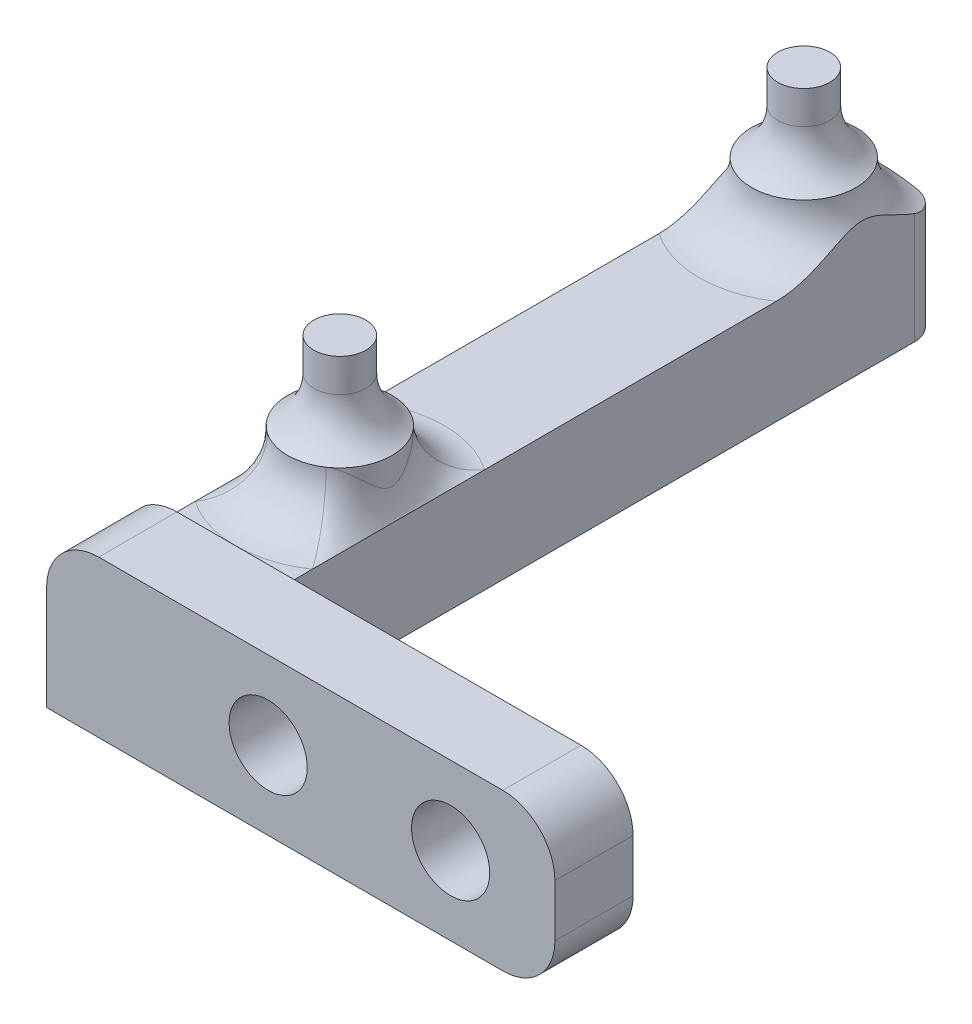
SolidWorks part; units mm, degrees
ref_plane "Front Plane" through (0, 0, 0) normal (0, 0, 1) x (1, 0, 0)
ref_plane "Top Plane" through (0, 0, 0) normal (0, 1, 0) x (1, 0, 0)
ref_plane "Right Plane" through (0, 0, 0) normal (1, 0, 0) x (0, 0, -1)
sketch "Sketch1" plane through (0, 0, 0) normal (0, 1, 0) x (1, 0, 0)
  line L0 (0, 0) -> (0, 15.9628) construction
  line L2 (-2.25, 15.1926) -> (2.25, 15.1926)
  line L3 (-2.25, 15.1926) -> (-2.25, -8.6074)
  line L4 (-2.25, -8.6074) -> (2.25, -8.6074)
  line L5 (2.25, 15.1926) -> (2.25, -8.6074)
  line L6 (-2.25, -8.6074) -> (2.25, -8.6074)
  line L7 (-2.25, -8.6074) -> (-2.25, -14.6074)
  line L8 (-2.25, -14.6074) -> (2.25, -14.6074)
  line L9 (2.25, -8.6074) -> (2.25, -14.6074)
  circle A0 centre (0, 12.1926) radius 2
  circle A1 centre (0, -5.6074) radius 2
  dimension "D1" = 2.25
  dimension "D3" = 4
  dimension "D4" = 4
  dimension "D5" = 3
  dimension "D6" = 3
  dimension "D7" = 17.8
  dimension "D2" = 4.5
  dimension "D8" = 6
extrude "Boss-Extrude1" add sketch "Sketch1" along normal blind 4 contours L9 L4 L7 L8 | A0 L2 L3 L4 L5 A1 region at (0, 0, -3.2926) region at (0, 0, 11.6074)
extrude "Boss-Extrude2" add sketch "Sketch1<3>" along normal blind 6 contours A1 | A0 L0 | L0 A0 region at (-0.8488, 0, -12.1926) region at (0.8488, 0, -12.1926) region at (0, 0, 5.6074)
sketch "Sketch1<3>" plane through (0, 0, 0) normal (0, 1, 0) x (1, 0, 0) same geometry as "Sketch1"
sketch "Sketch2" plane through (0, 6, 0) normal (0, 1, 0) x (1, 0, 0)
  circle A0 centre (0, 12.1926) radius 1
  circle A1 centre (0, -5.6074) radius 1
  dimension "D1" = 2
  dimension "D2" = 2
extrude "Boss-Extrude3" add sketch "Sketch2" along normal blind 3
fillet "Fillet1" radius 2 1 edges at (0, 6, 6.6074)
fillet "Fillet2" radius 2 1 edges at (0, 6, -11.1926)
fillet "Fillet3" radius 2 1 edges at (0, 4, 7.6074)
fillet "Fillet4" radius 2 1 edges at (0, 4, -10.1926)
sketch "Sketch3" plane through (2.25, 0, 0) normal (1, 0, 0) x (0, 0, -1)
  line L0 (15.1926, 0) -> (-14.6074, 0) construction
  line L1 (-14.6074, 4) -> (-11.6074, 4)
  line L2 (-14.6074, 4) -> (-14.6074, 0)
  line L3 (-14.6074, 0) -> (-11.6074, 0)
  line L4 (-11.6074, 4) -> (-11.6074, 0)
  dimension "D1" = 3
extrude "Boss-Extrude4" add sketch "Sketch3" along normal blind 15
sketch "Sketch5" plane through (0, 4, 0) normal (0, 1, 0) x (1, 0, 0)
  line L0 (-2.25, -14.6074) -> (17.25, -14.6074) construction
  line L1 (-2.25, -14.6074) -> (2.25, -14.6074)
  line L2 (-2.25, -14.6074) -> (-2.25, -11.6074)
  line L3 (-2.25, -11.6074) -> (2.25, -11.6074)
  line L4 (2.25, -14.6074) -> (2.25, -11.6074)
extrude "Boss-Extrude5" add sketch "Sketch5" along normal blind 2
sketch "Sketch7" plane through (2.25, 0, 0) normal (1, 0, 0) x (0, 0, -1)
  line L1 (-11.6074, 6) -> (-14.6074, 6)
  line L2 (-11.6074, 6) -> (-11.6074, 4)
  line L3 (-11.6074, 4) -> (-14.6074, 4)
  line L4 (-14.6074, 6) -> (-14.6074, 4)
extrude "Boss-Extrude6" add sketch "Sketch7" along normal up to surface (15 mm away) up to face at (17.25, 2, 13.1074)
sketch "Sketch8" plane through (0, 0, 11.6074) normal (0, 0, -1) x (-1, 0, 0)
  line L0 (-17.25, 3) -> (4.7513, 3) construction
  line L1 (-17.25, 0) -> (-17.25, 6) construction
  line L2 (-2.25, 0) -> (-2.25, 4) construction
  circle A0 centre (-6.25, 3) radius 1.5
  circle A1 centre (-13.25, 3) radius 1.5
  dimension "D1" = 3
  dimension "D2" = 3
  dimension "D3" = 4
  dimension "D4" = 4
extrude "Cut-Extrude1" cut sketch "Sketch8" against normal through all
fillet "Fillet12" radius 2 2 edges at (2.25, 2, 11.6074) (0, 4, 11.6074)
fillet "Fillet13" radius 2 1 edges at (-2.25, 6, 13.1074)
fillet "Fillet14" radius 2 2 edges at (17.25, 6, 13.1074) (17.25, 0, 13.1074)
fillet "Fillet16" radius 1 2 edges at (-2.25, 2.0078, -15.1926) (2.25, 2.0078, -15.1926)
